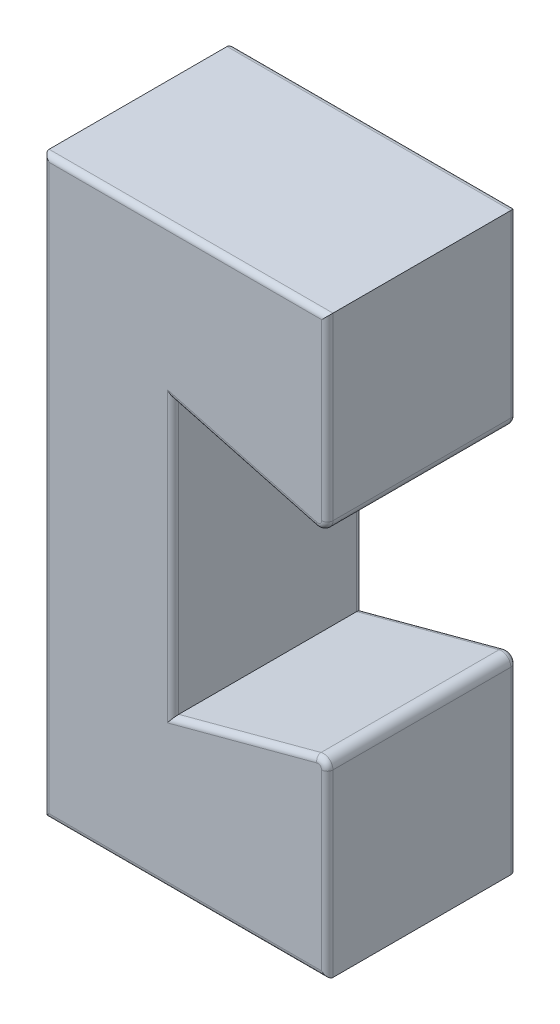
SolidWorks part; units mm, degrees
ref_plane "Plan de face" through (0, 0, 0) normal (0, 0, 1) x (1, 0, 0)
ref_plane "Plan de dessus" through (0, 0, 0) normal (0, 1, 0) x (1, 0, 0)
ref_plane "Plan de droite" through (0, 0, 0) normal (1, 0, 0) x (0, 0, -1)
sketch "Esquisse1" plane through (0, 0, 0) normal (0, 0, 1) x (1, 0, 0)
  line L0 (15, 20.25) -> (6.85, 22.4338)
  line L1 (0, 0) -> (15, 0)
  line L2 (0, 0) -> (0, 30.4)
  line L3 (0, 30.4) -> (15, 30.4)
  line L4 (15, 0) -> (15, 10.15)
  line L5 (6.85, 22.4338) -> (6.85, 7.9662)
  line L6 (6.85, 7.9662) -> (15, 10.15)
  line L7 (15, 20.25) -> (15, 30.4)
  dimension "D1" = 10.1
  dimension "D2" = 75
  dimension "D3" = 75
  dimension "D4" = 8.15
  dimension "D5" = 30.4
  dimension "D6" = 10.15
  dimension "D7" = 15
extrude "Boss.-Extru.1" add sketch "Esquisse1" along normal blind 10
fillet "Congé1" radius 0.3 16 edges at (7.5, 0, 0) (15, 5.075, 0) (10.925, 9.0581, 0) (6.85, 15.2, 0) (10.925, 21.3419, 0) (15, 25.325, 0) (7.5, 30.4, 0) (0, 15.2, 0) (7.5, 30.4, 10) (15, 25.325, 10) (10.925, 21.3419, 10) (6.85, 15.2, 10) (10.925, 9.0581, 10) (15, 5.075, 10) (7.5, 0, 10) (0, 15.2, 10)
fillet "Congé2" radius 0.5 6 edges at (14.9121, 20.3645, 0.0879) (14.9121, 20.3645, 9.9121) (14.9121, 10.0355, 0.0879) (14.9121, 10.0355, 9.9121) (15, 10.15, 5) (15, 20.25, 5)
